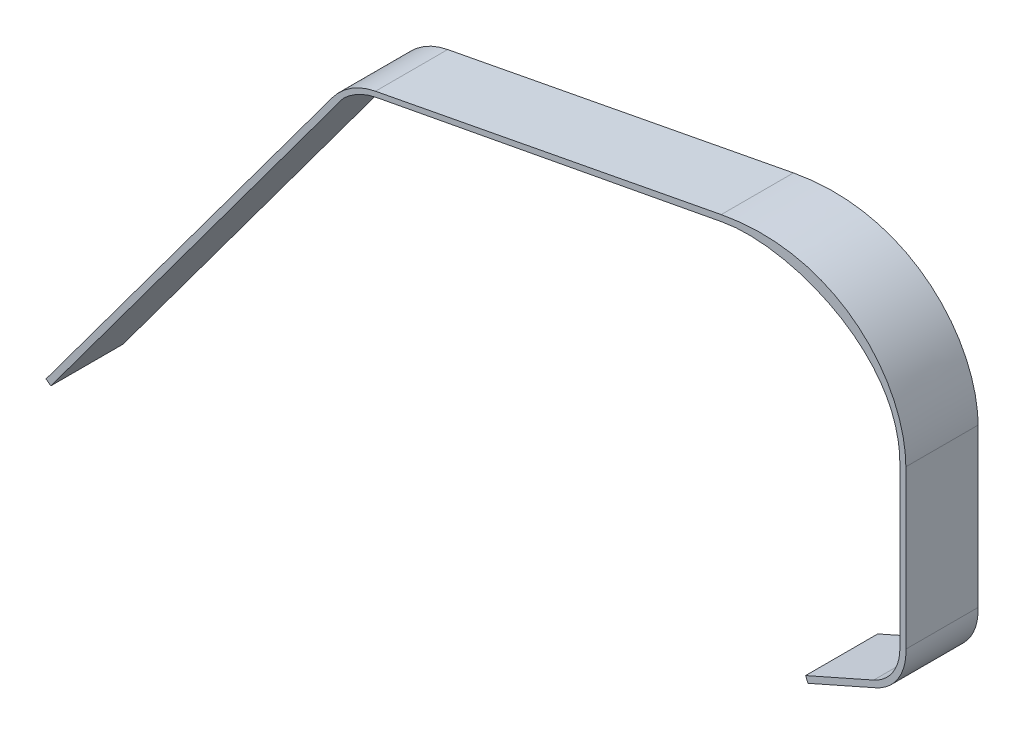
SolidWorks part; units mm, degrees
ref_plane "Front Plane" through (0, 0, 0) normal (0, 0, 1) x (1, 0, 0)
ref_plane "Top Plane" through (0, 0, 0) normal (0, 1, 0) x (1, 0, 0)
ref_plane "Right Plane" through (0, 0, 0) normal (1, 0, 0) x (0, 0, -1)
sketch "Sketch1" plane through (0, 0, 0) normal (0, 0, 1) x (1, 0, 0)
  line L0 (-6.9353, 36.3108) -> (175.5418, 71.1636)
  line L1 (0, 0) -> (17.6031, 3.3622) construction
  line L6 (-6.9353, 36.3108) -> (0, 0) construction
  line L9 (271.9391, -80.1313) -> (246.5741, -80.1313) construction
  line L11 (220.0498, -117.2908) -> (221.3351, -120.194)
  line L12 (272.9551, 4.5708) -> (272.9551, -78.7725)
  line L13 (262.5886, -116.3045) -> (259.8191, -110.0488) construction
  line L14 (221.3351, -120.194) -> (257.2678, -104.286)
  line L15 (-29.7121, 21.9946) -> (-27.2242, 20.153) construction
  line L19 (-29.7121, 21.9946) -> (-180.8365, -182.1558)
  line L20 (-180.8365, -182.1558) -> (-178.2846, -184.0449)
  line L21 (272.9551, -78.7725) -> (15.6856, -80.1313) construction
  line L22 (220.0498, -117.2908) -> (255.9825, -101.3828)
  line L24 (269.8151, -80.1313) -> (269.8151, 4.5708)
  line L26 (-29.7121, 21.9946) -> (-26.0187, 23.6348) construction
  line L27 (-23.978, 24.5411) -> (-178.2846, -184.0449)
  line L28 (175.5418, 71.1636) -> (200.98, -62.022) construction
  line L29 (272.9551, 4.5708) -> (188.2609, 4.5708) construction
  line L30 (226.5161, 80.8996) -> (124.3234, 61.381) construction
  line L31 (272.9551, -12.4405) -> (272.9551, 46.9396) construction
  line L33 (269.8151, -19.4747) -> (269.8151, 58.9292) construction
  line L34 (176.1375, 68.045) -> (-6.4369, 33.7013)
  arc A0 (-29.7121, 21.9946) -> (-6.9353, 36.3108) centre (0, 0) cw
  arc A5 (272.9551, -78.7725) -> (257.2678, -104.286) centre (246.5741, -80.1313) cw
  arc A6 (255.9825, -101.3828) -> (269.8151, -80.1313) centre (246.5741, -80.1313) ccw
  arc A8 (-6.4369, 33.7013) -> (-23.978, 24.5411) centre (0, 0) ccw
  circle A9 centre (-21.4316, -40.8727) radius 61.3 construction
  arc A10 (-190.1171, -186.0404) -> (-190.1067, -160.6404) centre (-190.1119, -173.3404) ccw construction
  circle A13 centre (231.071, -129.7727) radius 12.7 construction
  spline S0 degree 3 poles (175.5418, 71.1636) (238.0069, 83.0944) (272.9551, 41.6834) (272.9551, 4.5708) knots 0 0 0 0 1 1 1 1
  spline S1 degree 3 poles (176.1375, 68.045) (211.0177, 74.7071) (269.8151, 53.3746) (269.8151, 4.5708) knots 0 0 0 0 1 1 1 1
  point P4 (269.7801, -94.6575)
  point P8 (269.8151, -82.2857)
  point P17 (259.2359, -104.5153)
  point P25 (257.2678, -103.8855)
  dimension "D5" = 36.9672
  dimension "D8" = 26.416
  dimension "D1" = 254
  dimension "D2" = 3.175
  dimension "D7" = 3.175
extrude "Boss-Extrude1" add sketch "Sketch1" along normal blind 38.1 contours L0 A0 region at (84.4011, 53.2248, 0)
